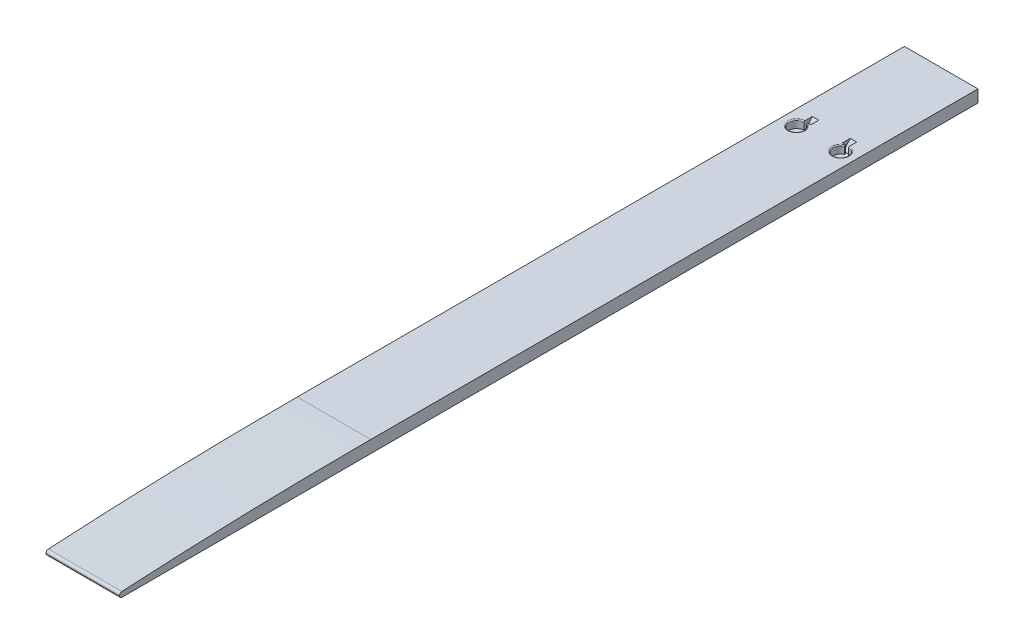
SolidWorks part; units mm, degrees
other "标注1"
sketch "草图6" plane through (0, 5, 350) normal (-0.6393, 0.5849, 0.4992) x (0.7619, 0.3939, 0.5141)
sketch "草图7" plane through (0, 5, 350) normal (-0.6393, 0.5849, 0.4992) x (0.7619, 0.3939, 0.5141)
sketch "草图8" plane through (0, 5, 350) normal (-0.6393, 0.5849, 0.4992) x (0.7619, 0.3939, 0.5141)
sketch "草图9" plane through (0, 5, 350) normal (-0.6393, 0.5849, 0.4992) x (0.7619, 0.3939, 0.5141)
sketch "草图11" plane through (0, 5, 350) normal (-0.6393, 0.5849, 0.4992) x (0.7619, 0.3939, 0.5141)
ref_plane "前视基准面" through (0, 0, 0) normal (0, 0, 1) x (1, 0, 0)
ref_plane "上视基准面" through (0, 0, 0) normal (0, 1, 0) x (1, 0, 0)
ref_plane "右视基准面" through (0, 0, 0) normal (1, 0, 0) x (0, 0, -1)
other "Configuration Table"
sketch "草图1" plane through (0, 0, 0) normal (1, 0, 0) x (0, 0, -1)
  line L0 (0, 0) -> (-350, 0)
  line L5 (0, 5) -> (0, 0)
  line L6 (-300, 5) -> (0, 5)
  line L7 (-350, 0) -> (-350, 2)
  line L8 (-350, 2) -> (-300, 5)
  dimension "D1" = 350
  dimension "D2" = 5
  dimension "D3" = 2
  dimension "D7" = 50
extrude "凸台-拉伸1" add sketch "草图1" along normal blind 30
fillet "圆角1" radius 1750 1 edges at (15, 5, 300)
sketch "草图4" plane through (0, 5, 0) normal (0, 1, 0) x (1, 0, 0)
  line L0 (30, 0) -> (30, -247.5744) construction
  line L2 (15, 0) -> (15, -26.6679) construction
  line L3 (30, 0) -> (0, 0) construction
  line L4 (30, -350) -> (0, -350) construction
  circle A0 centre (24, -50) radius 3.1
  circle A1 centre (6, -50) radius 3.1
  dimension "D2" = 6.2
  dimension "D1" = 6
  dimension "D3" = 300
extrude "切除-拉伸3" cut sketch "草图4" against normal blind 3.2
fillet "圆角4" radius 0.4 2 edges at (24, 5, 53.1) (6, 5, 46.9)
sketch "草图5" plane through (0, 0, 0) normal (0, 0, -1) x (-1, 0, 0)
  line L0 (0, 0) -> (0, 5) construction
  line L1 (-25, 3.5) -> (-5, 3.5)
  line L2 (-25, 3.5) -> (-25, 1.5)
  line L3 (-25, 1.5) -> (-5, 1.5)
  line L4 (-5, 3.5) -> (-5, 1.5)
  line L5 (-30, 0) -> (-30, 5) construction
  line L6 (-30, 5) -> (0, 5) construction
  line L7 (-30, 0) -> (0, 0) construction
  dimension "D1" = 5
  dimension "D2" = 5
  dimension "D3" = 1.5
  dimension "D4" = 1.5
extrude "切除-拉伸4" cut sketch "草图5" against normal blind 25
fillet "圆角5" radius 1 2 edges at (15, 0, 350) (15, 2, 350)
fillet "圆角6" radius 1 2 edges at (15, 1.5, 0) (15, 3.5, 0)
sketch "草图10" plane through (0, 5, 0) normal (0, 1, 0) x (1, 0, 0)
  line L0 (15, 0) -> (15, -33.6975) construction
  line L1 (7.3025, -46.7514) -> (8.5863, -46.7514)
  line L2 (5.9775, -46.5001) -> (5.9775, -43.5001)
  line L3 (5.9775, -43.5001) -> (8.5863, -43.5001)
  line L4 (8.5863, -46.7514) -> (8.5863, -43.5001)
  line L5 (30, 0) -> (0, 0) construction
  line L6 (24.0225, -46.5001) -> (24.0225, -43.5001)
  line L7 (24.0225, -43.5001) -> (21.4137, -43.5001)
  line L8 (21.4137, -46.7514) -> (21.4137, -43.5001)
  line L9 (22.6975, -46.7514) -> (21.4137, -46.7514)
  line L10 (5.9775, -46.5001) -> (5.9775, -46.9001)
  line L11 (7.3025, -46.7514) -> (7.3025, -47.1869)
  line L12 (22.6975, -46.7514) -> (22.6975, -47.1869)
  line L13 (24.0225, -46.5001) -> (24.0225, -46.9001)
  circle A0 centre (6, -50) radius 3.5 construction
  circle A3 centre (6, -50) radius 3.1 construction
  arc A4 (7.3025, -47.1869) -> (5.9775, -46.9001) centre (6, -50) ccw
  circle A5 centre (24, -50) radius 3.1 construction
  arc A6 (24.0225, -46.9001) -> (22.6975, -47.1869) centre (24, -50) ccw
  dimension "D1" = 2.6088
  dimension "D2" = 3
extrude "切除-拉伸5" cut sketch "草图10" against normal up to surface (3.2 mm away) up to face at (6, 1.8, 46.9)
chamfer "倒角1" distance 3.2 angle 40 2 edges at (22.7181, 1.8, 43.5001) (7.2819, 1.8, 43.5001) first distance on face at (22.7181, 3.4, 43.5001) first distance on face at (7.2819, 3.4, 43.5001)
